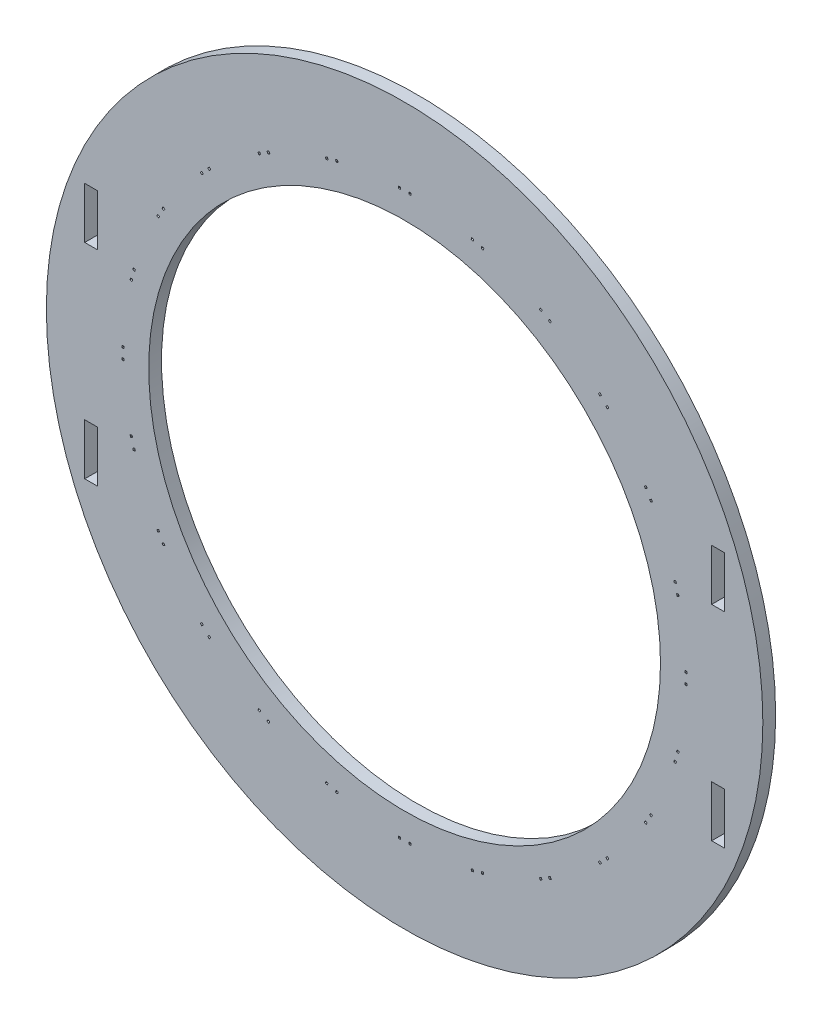
SolidWorks part; units mm, degrees
ref_plane "Front Plane" through (0, 0, 0) normal (0, 0, 1) x (1, 0, 0)
ref_plane "Top Plane" through (0, 0, 0) normal (0, 1, 0) x (1, 0, 0)
ref_plane "Right Plane" through (0, 0, 0) normal (1, 0, 0) x (0, 0, -1)
sketch "Sketch1" plane through (0, 0, 0) normal (0, 0, 1) x (1, 0, 0)
  line L0 (0, 63.5) -> (0, 69.85) construction
  line L1 (-1.3017, 69.85) -> (1.3017, 69.85) construction
  line L2 (1.5684, 69.5833) -> (1.035, 70.1167) construction
  line L3 (-1.5684, 70.1167) -> (-1.035, 70.1167)
  line L4 (-1.5684, 70.1167) -> (-1.5684, 69.5833)
  line L5 (-1.5684, 69.5833) -> (-1.035, 69.5833)
  line L6 (-1.035, 70.1167) -> (-1.035, 69.5833)
  line L7 (-1.5684, 70.1167) -> (-1.035, 69.5833) construction
  line L8 (-1.5684, 69.5833) -> (-1.035, 70.1167) construction
  line L9 (1.5684, 70.1167) -> (1.035, 69.5833) construction
  line L10 (1.035, 70.1167) -> (1.035, 69.5833)
  line L11 (1.5684, 69.5833) -> (1.035, 69.5833)
  line L12 (1.5684, 70.1167) -> (1.5684, 69.5833)
  line L13 (1.5684, 70.1167) -> (1.035, 70.1167)
  line L14 (16.6325, 68.1335) -> (17.1478, 67.9954)
  line L15 (16.6325, 68.1335) -> (16.4945, 67.6183)
  line L16 (16.4945, 67.6183) -> (17.0097, 67.4802)
  line L17 (17.1478, 67.9954) -> (17.0097, 67.4802)
  line L18 (19.1473, 67.4596) -> (19.0093, 66.9444)
  line L19 (19.5245, 66.8064) -> (19.0093, 66.9444)
  line L20 (19.6625, 67.3216) -> (19.5245, 66.8064)
  line L21 (19.6625, 67.3216) -> (19.1473, 67.4596)
  line L22 (19.5245, 66.8064) -> (19.1473, 67.4596) construction
  line L23 (16.6325, 68.1335) -> (17.0097, 67.4802) construction
  line L24 (16.4945, 67.6183) -> (17.1478, 67.9954) construction
  line L25 (19.6625, 67.3216) -> (19.0093, 66.9444) construction
  line L26 (33.7, 61.5071) -> (34.162, 61.2404)
  line L27 (33.7, 61.5071) -> (33.4333, 61.0451)
  line L28 (33.4333, 61.0451) -> (33.8953, 60.7784)
  line L29 (34.162, 61.2404) -> (33.8953, 60.7784)
  line L30 (35.9547, 60.2053) -> (35.688, 59.7434)
  line L31 (36.15, 59.4767) -> (35.688, 59.7434)
  line L32 (36.4167, 59.9386) -> (36.15, 59.4767)
  line L33 (36.4167, 59.9386) -> (35.9547, 60.2053)
  line L34 (36.15, 59.4767) -> (35.9547, 60.2053) construction
  line L35 (33.7, 61.5071) -> (33.8953, 60.7784) construction
  line L36 (33.4333, 61.0451) -> (34.162, 61.2404) construction
  line L37 (36.4167, 59.9386) -> (35.688, 59.7434) construction
  line L38 (48.4709, 50.6891) -> (48.8481, 50.3119)
  line L39 (48.4709, 50.6891) -> (48.0938, 50.3119)
  line L40 (48.0938, 50.3119) -> (48.4709, 49.9347)
  line L41 (48.8481, 50.3119) -> (48.4709, 49.9347)
  line L42 (50.3119, 48.8481) -> (49.9347, 48.4709)
  line L43 (50.3119, 48.0938) -> (49.9347, 48.4709)
  line L44 (50.6891, 48.4709) -> (50.3119, 48.0938)
  line L45 (50.6891, 48.4709) -> (50.3119, 48.8481)
  line L46 (50.3119, 48.0938) -> (50.3119, 48.8481) construction
  line L47 (48.4709, 50.6891) -> (48.4709, 49.9347) construction
  line L48 (48.0938, 50.3119) -> (48.8481, 50.3119) construction
  line L49 (50.6891, 48.4709) -> (49.9347, 48.4709) construction
  line L50 (59.9386, 36.4167) -> (60.2053, 35.9547)
  line L51 (59.9386, 36.4167) -> (59.4767, 36.15)
  line L52 (59.4767, 36.15) -> (59.7434, 35.688)
  line L53 (60.2053, 35.9547) -> (59.7434, 35.688)
  line L54 (61.2404, 34.162) -> (60.7784, 33.8953)
  line L55 (61.0451, 33.4333) -> (60.7784, 33.8953)
  line L56 (61.5071, 33.7) -> (61.0451, 33.4333)
  line L57 (61.5071, 33.7) -> (61.2404, 34.162)
  line L58 (61.0451, 33.4333) -> (61.2404, 34.162) construction
  line L59 (59.9386, 36.4167) -> (59.7434, 35.688) construction
  line L60 (59.4767, 36.15) -> (60.2053, 35.9547) construction
  line L61 (61.5071, 33.7) -> (60.7784, 33.8953) construction
  line L62 (67.3216, 19.6625) -> (67.4596, 19.1473)
  line L63 (67.3216, 19.6625) -> (66.8064, 19.5245)
  line L64 (66.8064, 19.5245) -> (66.9444, 19.0093)
  line L65 (67.4596, 19.1473) -> (66.9444, 19.0093)
  line L66 (67.9954, 17.1478) -> (67.4802, 17.0097)
  line L67 (67.6183, 16.4945) -> (67.4802, 17.0097)
  line L68 (68.1335, 16.6325) -> (67.6183, 16.4945)
  line L69 (68.1335, 16.6325) -> (67.9954, 17.1478)
  line L70 (67.6183, 16.4945) -> (67.9954, 17.1478) construction
  line L71 (67.3216, 19.6625) -> (66.9444, 19.0093) construction
  line L72 (66.8064, 19.5245) -> (67.4596, 19.1473) construction
  line L73 (68.1335, 16.6325) -> (67.4802, 17.0097) construction
  line L74 (70.1167, 1.5685) -> (70.1167, 1.0351)
  line L75 (70.1167, 1.5685) -> (69.5833, 1.5685)
  line L76 (69.5833, 1.5685) -> (69.5833, 1.0351)
  line L77 (70.1167, 1.0351) -> (69.5833, 1.0351)
  line L78 (70.1167, -1.035) -> (69.5833, -1.035)
  line L79 (69.5833, -1.5684) -> (69.5833, -1.035)
  line L80 (70.1167, -1.5684) -> (69.5833, -1.5684)
  line L81 (70.1167, -1.5684) -> (70.1167, -1.035)
  line L82 (69.5833, -1.5684) -> (70.1167, -1.035) construction
  line L83 (70.1167, 1.5685) -> (69.5833, 1.0351) construction
  line L84 (69.5833, 1.5685) -> (70.1167, 1.0351) construction
  line L85 (70.1167, -1.5684) -> (69.5833, -1.035) construction
  line L86 (68.1335, -16.6325) -> (67.9954, -17.1478)
  line L87 (68.1335, -16.6325) -> (67.6183, -16.4945)
  line L88 (67.6183, -16.4945) -> (67.4802, -17.0097)
  line L89 (67.9954, -17.1478) -> (67.4802, -17.0097)
  line L90 (67.4596, -19.1473) -> (66.9444, -19.0093)
  line L91 (66.8064, -19.5245) -> (66.9444, -19.0093)
  line L92 (67.3216, -19.6625) -> (66.8064, -19.5245)
  line L93 (67.3216, -19.6625) -> (67.4596, -19.1473)
  line L94 (66.8064, -19.5245) -> (67.4596, -19.1473) construction
  line L95 (68.1335, -16.6325) -> (67.4802, -17.0097) construction
  line L96 (67.6183, -16.4945) -> (67.9954, -17.1478) construction
  line L97 (67.3216, -19.6625) -> (66.9444, -19.0093) construction
  line L98 (61.5071, -33.7) -> (61.2404, -34.162)
  line L99 (61.5071, -33.7) -> (61.0451, -33.4333)
  line L100 (61.0451, -33.4333) -> (60.7784, -33.8953)
  line L101 (61.2404, -34.162) -> (60.7784, -33.8953)
  line L102 (60.2053, -35.9547) -> (59.7434, -35.688)
  line L103 (59.4767, -36.15) -> (59.7434, -35.688)
  line L104 (59.9386, -36.4167) -> (59.4767, -36.15)
  line L105 (59.9386, -36.4167) -> (60.2053, -35.9547)
  line L106 (59.4767, -36.15) -> (60.2053, -35.9547) construction
  line L107 (61.5071, -33.7) -> (60.7784, -33.8953) construction
  line L108 (61.0451, -33.4333) -> (61.2404, -34.162) construction
  line L109 (59.9386, -36.4167) -> (59.7434, -35.688) construction
  line L110 (50.6891, -48.4709) -> (50.3119, -48.8481)
  line L111 (50.6891, -48.4709) -> (50.3119, -48.0938)
  line L112 (50.3119, -48.0938) -> (49.9347, -48.4709)
  line L113 (50.3119, -48.8481) -> (49.9347, -48.4709)
  line L114 (48.8481, -50.3119) -> (48.4709, -49.9347)
  line L115 (48.0938, -50.3119) -> (48.4709, -49.9347)
  line L116 (48.4709, -50.6891) -> (48.0938, -50.3119)
  line L117 (48.4709, -50.6891) -> (48.8481, -50.3119)
  line L118 (48.0938, -50.3119) -> (48.8481, -50.3119) construction
  line L119 (50.6891, -48.4709) -> (49.9347, -48.4709) construction
  line L120 (50.3119, -48.0938) -> (50.3119, -48.8481) construction
  line L121 (48.4709, -50.6891) -> (48.4709, -49.9347) construction
  line L122 (36.4167, -59.9386) -> (35.9547, -60.2053)
  line L123 (36.4167, -59.9386) -> (36.15, -59.4767)
  line L124 (36.15, -59.4767) -> (35.688, -59.7434)
  line L125 (35.9547, -60.2053) -> (35.688, -59.7434)
  line L126 (34.162, -61.2404) -> (33.8953, -60.7784)
  line L127 (33.4333, -61.0451) -> (33.8953, -60.7784)
  line L128 (33.7, -61.5071) -> (33.4333, -61.0451)
  line L129 (33.7, -61.5071) -> (34.162, -61.2404)
  line L130 (33.4333, -61.0451) -> (34.162, -61.2404) construction
  line L131 (36.4167, -59.9386) -> (35.688, -59.7434) construction
  line L132 (36.15, -59.4767) -> (35.9547, -60.2053) construction
  line L133 (33.7, -61.5071) -> (33.8953, -60.7784) construction
  line L134 (19.6625, -67.3216) -> (19.1473, -67.4596)
  line L135 (19.6625, -67.3216) -> (19.5245, -66.8064)
  line L136 (19.5245, -66.8064) -> (19.0093, -66.9444)
  line L137 (19.1473, -67.4596) -> (19.0093, -66.9444)
  line L138 (17.1478, -67.9954) -> (17.0097, -67.4802)
  line L139 (16.4945, -67.6183) -> (17.0097, -67.4802)
  line L140 (16.6325, -68.1335) -> (16.4945, -67.6183)
  line L141 (16.6325, -68.1335) -> (17.1478, -67.9954)
  line L142 (16.4945, -67.6183) -> (17.1478, -67.9954) construction
  line L143 (19.6625, -67.3216) -> (19.0093, -66.9444) construction
  line L144 (19.5245, -66.8064) -> (19.1473, -67.4596) construction
  line L145 (16.6325, -68.1335) -> (17.0097, -67.4802) construction
  line L146 (1.5685, -70.1167) -> (1.0351, -70.1167)
  line L147 (1.5685, -70.1167) -> (1.5685, -69.5833)
  line L148 (1.5685, -69.5833) -> (1.0351, -69.5833)
  line L149 (1.0351, -70.1167) -> (1.0351, -69.5833)
  line L150 (-1.035, -70.1167) -> (-1.035, -69.5833)
  line L151 (-1.5684, -69.5833) -> (-1.035, -69.5833)
  line L152 (-1.5684, -70.1167) -> (-1.5684, -69.5833)
  line L153 (-1.5684, -70.1167) -> (-1.035, -70.1167)
  line L154 (-1.5684, -69.5833) -> (-1.035, -70.1167) construction
  line L155 (1.5685, -70.1167) -> (1.0351, -69.5833) construction
  line L156 (1.5685, -69.5833) -> (1.0351, -70.1167) construction
  line L157 (-1.5684, -70.1167) -> (-1.035, -69.5833) construction
  line L158 (-16.6325, -68.1335) -> (-17.1478, -67.9954)
  line L159 (-16.6325, -68.1335) -> (-16.4945, -67.6183)
  line L160 (-16.4945, -67.6183) -> (-17.0097, -67.4802)
  line L161 (-17.1478, -67.9954) -> (-17.0097, -67.4802)
  line L162 (-19.1473, -67.4596) -> (-19.0093, -66.9444)
  line L163 (-19.5245, -66.8064) -> (-19.0093, -66.9444)
  line L164 (-19.6625, -67.3216) -> (-19.5245, -66.8064)
  line L165 (-19.6625, -67.3216) -> (-19.1473, -67.4596)
  line L166 (-19.5245, -66.8064) -> (-19.1473, -67.4596) construction
  line L167 (-16.6325, -68.1335) -> (-17.0097, -67.4802) construction
  line L168 (-16.4945, -67.6183) -> (-17.1478, -67.9954) construction
  line L169 (-19.6625, -67.3216) -> (-19.0093, -66.9444) construction
  line L170 (-33.7, -61.5071) -> (-34.162, -61.2404)
  line L171 (-33.7, -61.5071) -> (-33.4333, -61.0451)
  line L172 (-33.4333, -61.0451) -> (-33.8953, -60.7784)
  line L173 (-34.162, -61.2404) -> (-33.8953, -60.7784)
  line L174 (-35.9547, -60.2053) -> (-35.688, -59.7434)
  line L175 (-36.15, -59.4767) -> (-35.688, -59.7434)
  line L176 (-36.4167, -59.9386) -> (-36.15, -59.4767)
  line L177 (-36.4167, -59.9386) -> (-35.9547, -60.2053)
  line L178 (-36.15, -59.4767) -> (-35.9547, -60.2053) construction
  line L179 (-33.7, -61.5071) -> (-33.8953, -60.7784) construction
  line L180 (-33.4333, -61.0451) -> (-34.162, -61.2404) construction
  line L181 (-36.4167, -59.9386) -> (-35.688, -59.7434) construction
  line L182 (-48.4709, -50.6891) -> (-48.8481, -50.3119)
  line L183 (-48.4709, -50.6891) -> (-48.0938, -50.3119)
  line L184 (-48.0938, -50.3119) -> (-48.4709, -49.9347)
  line L185 (-48.8481, -50.3119) -> (-48.4709, -49.9347)
  line L186 (-50.3119, -48.8481) -> (-49.9347, -48.4709)
  line L187 (-50.3119, -48.0938) -> (-49.9347, -48.4709)
  line L188 (-50.6891, -48.4709) -> (-50.3119, -48.0938)
  line L189 (-50.6891, -48.4709) -> (-50.3119, -48.8481)
  line L190 (-50.3119, -48.0938) -> (-50.3119, -48.8481) construction
  line L191 (-48.4709, -50.6891) -> (-48.4709, -49.9347) construction
  line L192 (-48.0938, -50.3119) -> (-48.8481, -50.3119) construction
  line L193 (-50.6891, -48.4709) -> (-49.9347, -48.4709) construction
  line L194 (-59.9386, -36.4167) -> (-60.2053, -35.9547)
  line L195 (-59.9386, -36.4167) -> (-59.4767, -36.15)
  line L196 (-59.4767, -36.15) -> (-59.7434, -35.688)
  line L197 (-60.2053, -35.9547) -> (-59.7434, -35.688)
  line L198 (-61.2404, -34.162) -> (-60.7784, -33.8953)
  line L199 (-61.0451, -33.4333) -> (-60.7784, -33.8953)
  line L200 (-61.5071, -33.7) -> (-61.0451, -33.4333)
  line L201 (-61.5071, -33.7) -> (-61.2404, -34.162)
  line L202 (-61.0451, -33.4333) -> (-61.2404, -34.162) construction
  line L203 (-59.9386, -36.4167) -> (-59.7434, -35.688) construction
  line L204 (-59.4767, -36.15) -> (-60.2053, -35.9547) construction
  line L205 (-61.5071, -33.7) -> (-60.7784, -33.8953) construction
  line L206 (-67.3216, -19.6625) -> (-67.4596, -19.1473)
  line L207 (-67.3216, -19.6625) -> (-66.8064, -19.5245)
  line L208 (-66.8064, -19.5245) -> (-66.9444, -19.0093)
  line L209 (-67.4596, -19.1473) -> (-66.9444, -19.0093)
  line L210 (-67.9954, -17.1478) -> (-67.4802, -17.0097)
  line L211 (-67.6183, -16.4945) -> (-67.4802, -17.0097)
  line L212 (-68.1335, -16.6325) -> (-67.6183, -16.4945)
  line L213 (-68.1335, -16.6325) -> (-67.9954, -17.1478)
  line L214 (-67.6183, -16.4945) -> (-67.9954, -17.1478) construction
  line L215 (-67.3216, -19.6625) -> (-66.9444, -19.0093) construction
  line L216 (-66.8064, -19.5245) -> (-67.4596, -19.1473) construction
  line L217 (-68.1335, -16.6325) -> (-67.4802, -17.0097) construction
  line L218 (-70.1167, -1.5685) -> (-70.1167, -1.0351)
  line L219 (-70.1167, -1.5685) -> (-69.5833, -1.5685)
  line L220 (-69.5833, -1.5685) -> (-69.5833, -1.0351)
  line L221 (-70.1167, -1.0351) -> (-69.5833, -1.0351)
  line L222 (-70.1167, 1.035) -> (-69.5833, 1.035)
  line L223 (-69.5833, 1.5684) -> (-69.5833, 1.035)
  line L224 (-70.1167, 1.5684) -> (-69.5833, 1.5684)
  line L225 (-70.1167, 1.5684) -> (-70.1167, 1.035)
  line L226 (-69.5833, 1.5684) -> (-70.1167, 1.035) construction
  line L227 (-70.1167, -1.5685) -> (-69.5833, -1.0351) construction
  line L228 (-69.5833, -1.5685) -> (-70.1167, -1.0351) construction
  line L229 (-70.1167, 1.5684) -> (-69.5833, 1.035) construction
  line L230 (-68.1335, 16.6325) -> (-67.9954, 17.1478)
  line L231 (-68.1335, 16.6325) -> (-67.6183, 16.4945)
  line L232 (-67.6183, 16.4945) -> (-67.4802, 17.0097)
  line L233 (-67.9954, 17.1478) -> (-67.4802, 17.0097)
  line L234 (-67.4596, 19.1473) -> (-66.9444, 19.0093)
  line L235 (-66.8064, 19.5245) -> (-66.9444, 19.0093)
  line L236 (-67.3216, 19.6625) -> (-66.8064, 19.5245)
  line L237 (-67.3216, 19.6625) -> (-67.4596, 19.1473)
  line L238 (-66.8064, 19.5245) -> (-67.4596, 19.1473) construction
  line L239 (-68.1335, 16.6325) -> (-67.4802, 17.0097) construction
  line L240 (-67.6183, 16.4945) -> (-67.9954, 17.1478) construction
  line L241 (-67.3216, 19.6625) -> (-66.9444, 19.0093) construction
  line L242 (-61.5071, 33.7) -> (-61.2404, 34.162)
  line L243 (-61.5071, 33.7) -> (-61.0451, 33.4333)
  line L244 (-61.0451, 33.4333) -> (-60.7784, 33.8953)
  line L245 (-61.2404, 34.162) -> (-60.7784, 33.8953)
  line L246 (-60.2053, 35.9547) -> (-59.7434, 35.688)
  line L247 (-59.4767, 36.15) -> (-59.7434, 35.688)
  line L248 (-59.9386, 36.4167) -> (-59.4767, 36.15)
  line L249 (-59.9386, 36.4167) -> (-60.2053, 35.9547)
  line L250 (-59.4767, 36.15) -> (-60.2053, 35.9547) construction
  line L251 (-61.5071, 33.7) -> (-60.7784, 33.8953) construction
  line L252 (-61.0451, 33.4333) -> (-61.2404, 34.162) construction
  line L253 (-59.9386, 36.4167) -> (-59.7434, 35.688) construction
  line L254 (-50.6891, 48.4709) -> (-50.3119, 48.8481)
  line L255 (-50.6891, 48.4709) -> (-50.3119, 48.0938)
  line L256 (-50.3119, 48.0938) -> (-49.9347, 48.4709)
  line L257 (-50.3119, 48.8481) -> (-49.9347, 48.4709)
  line L258 (-48.8481, 50.3119) -> (-48.4709, 49.9347)
  line L259 (-48.0938, 50.3119) -> (-48.4709, 49.9347)
  line L260 (-48.4709, 50.6891) -> (-48.0938, 50.3119)
  line L261 (-48.4709, 50.6891) -> (-48.8481, 50.3119)
  line L262 (-48.0938, 50.3119) -> (-48.8481, 50.3119) construction
  line L263 (-50.6891, 48.4709) -> (-49.9347, 48.4709) construction
  line L264 (-50.3119, 48.0938) -> (-50.3119, 48.8481) construction
  line L265 (-48.4709, 50.6891) -> (-48.4709, 49.9347) construction
  line L266 (-36.4167, 59.9386) -> (-35.9547, 60.2053)
  line L267 (-36.4167, 59.9386) -> (-36.15, 59.4767)
  line L268 (-36.15, 59.4767) -> (-35.688, 59.7434)
  line L269 (-35.9547, 60.2053) -> (-35.688, 59.7434)
  line L270 (-34.162, 61.2404) -> (-33.8953, 60.7784)
  line L271 (-33.4333, 61.0451) -> (-33.8953, 60.7784)
  line L272 (-33.7, 61.5071) -> (-33.4333, 61.0451)
  line L273 (-33.7, 61.5071) -> (-34.162, 61.2404)
  line L274 (-33.4333, 61.0451) -> (-34.162, 61.2404) construction
  line L275 (-36.4167, 59.9386) -> (-35.688, 59.7434) construction
  line L276 (-36.15, 59.4767) -> (-35.9547, 60.2053) construction
  line L277 (-33.7, 61.5071) -> (-33.8953, 60.7784) construction
  line L278 (-19.6625, 67.3216) -> (-19.1473, 67.4596)
  line L279 (-19.6625, 67.3216) -> (-19.5245, 66.8064)
  line L280 (-19.5245, 66.8064) -> (-19.0093, 66.9444)
  line L281 (-19.1473, 67.4596) -> (-19.0093, 66.9444)
  line L282 (-17.1478, 67.9954) -> (-17.0097, 67.4802)
  line L283 (-16.4945, 67.6183) -> (-17.0097, 67.4802)
  line L284 (-16.6325, 68.1335) -> (-16.4945, 67.6183)
  line L285 (-16.6325, 68.1335) -> (-17.1478, 67.9954)
  line L286 (-16.4945, 67.6183) -> (-17.1478, 67.9954) construction
  line L287 (-19.6625, 67.3216) -> (-19.0093, 66.9444) construction
  line L288 (-19.5245, 66.8064) -> (-19.1473, 67.4596) construction
  line L289 (-16.6325, 68.1335) -> (-17.0097, 67.4802) construction
  line L290 (76.2, 31.7348) -> (76.2, -31.7652) construction
  line L291 (76.2, -31.7652) -> (79.375, -31.7652) construction
  line L292 (79.375, -31.7652) -> (79.375, 31.7348) construction
  line L293 (79.375, 31.7348) -> (76.2, 31.7348) construction
  line L294 (0, -1000) -> (0, 49000) construction
  line L295 (76.2, 31.7348) -> (79.375, 31.7348)
  line L296 (76.2, 31.7348) -> (76.2, 19.0348)
  line L297 (76.2, 19.0348) -> (79.375, 19.0348)
  line L298 (79.375, 31.7348) -> (79.375, 19.0348)
  line L299 (76.2, -19.0652) -> (79.375, -19.0652)
  line L300 (76.2, -19.0652) -> (76.2, -31.7652)
  line L301 (76.2, -31.7652) -> (79.375, -31.7652)
  line L302 (79.375, -19.0652) -> (79.375, -31.7652)
  line L303 (-79.375, 31.7348) -> (-76.2, 31.7348) construction
  line L304 (-79.375, -31.7652) -> (-79.375, 31.7348) construction
  line L305 (-76.2, -31.7652) -> (-79.375, -31.7652) construction
  line L306 (-76.2, 31.7348) -> (-76.2, -31.7652) construction
  line L307 (-79.375, -19.0652) -> (-79.375, -31.7652)
  line L308 (-76.2, -31.7652) -> (-79.375, -31.7652)
  line L309 (-76.2, -19.0652) -> (-76.2, -31.7652)
  line L310 (-76.2, -19.0652) -> (-79.375, -19.0652)
  line L311 (-79.375, 31.7348) -> (-79.375, 19.0348)
  line L312 (-76.2, 19.0348) -> (-79.375, 19.0348)
  line L313 (-76.2, 31.7348) -> (-76.2, 19.0348)
  line L314 (-76.2, 31.7348) -> (-79.375, 31.7348)
  circle A0 centre (0, 0) radius 63.5
  circle A1 centre (0, 0) radius 88.9
  point P8 (0, 69.85)
  dimension "D1" = 127
  dimension "D2" = 177.8
  dimension "D5" = 0.5334
  dimension "D3" = 2.6035
  dimension "D4" = 6.35
  dimension "D6" = 76.2
  dimension "D7" = 3.175
  dimension "D8" = 63.5
  dimension "D9" = 31.7348
  dimension "D10" = 12.7
  dimension "D11" = 12.7
extrude "Boss-Extrude1" add sketch "Sketch1" along normal blind 3.175
